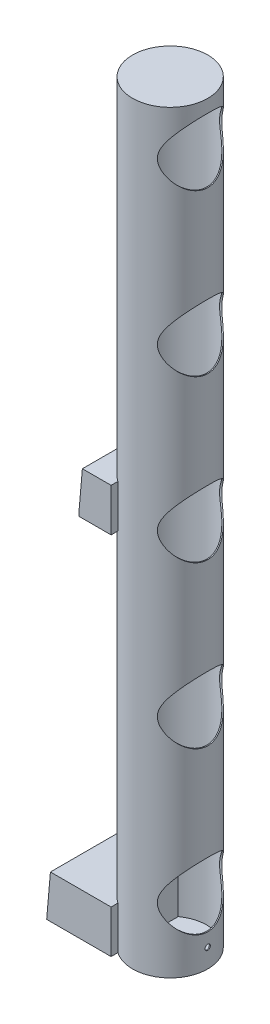
SolidWorks part; units mm, degrees
ref_plane "Спереди" through (0, 0, 0) normal (0, 0, 1) x (1, 0, 0)
ref_plane "Сверху" through (0, 0, 0) normal (0, 1, 0) x (1, 0, 0)
ref_plane "Справа" through (0, 0, 0) normal (1, 0, 0) x (0, 0, -1)
sketch "Эскиз2" plane through (0, 0, 0) normal (0, 1, 0) x (1, 0, 0)
  circle A0 centre (0, 0) radius 35
  circle A1 centre (0, 0) radius 34
  dimension "D1" = 70
  dimension "D2" = 68
extrude "Бобышка-Вытянуть1" add sketch "Эскиз2" along normal blind 700
sketch "Эскиз3" plane through (0, 0, 0) normal (0, -1, 0) x (1, 0, 0)
  circle A0 centre (0, 0) radius 35
extrude "Бобышка-Вытянуть2" add sketch "Эскиз3" along normal blind 1
sketch "Эскиз4" plane through (0, 700, 0) normal (0, 1, 0) x (1, 0, 0)
  circle A0 centre (0, 0) radius 35
extrude "Бобышка-Вытянуть3" add sketch "Эскиз4" along normal blind 1
sketch "Эскиз5" plane through (0, 0, 0) normal (1, 0, 0) x (0, 0, -1)
  line L0 (-35, -1) -> (35, -1) construction
  circle A0 centre (0, 16.5) radius 2.5
  circle A1 centre (0, 59) radius 30
  circle A2 centre (0, 209) radius 30
  circle A3 centre (0, 359) radius 30
  circle A4 centre (0, 509) radius 30
  circle A5 centre (0, 659) radius 30
  dimension "D1" = 5
  dimension "D2" = 15
  dimension "D3" = 60
  dimension "D4" = 60
  dimension "D6" = 150
  dimension "D5" = 5
extrude "Вырез-Вытянуть1" cut sketch "Эскиз5" along normal through all
sketch "Эскиз6" plane through (0, 0, 0) normal (1, 0, 0) x (0, 0, -1)
  line L0 (35, 701) -> (-35, 701) construction
  circle A0 centre (0, 686) radius 10
  dimension "D1" = 20
  dimension "D2" = 15
extrude "Вырез-Вытянуть2" cut sketch "Эскиз6" against normal through all
sketch "Эскиз7" plane through (0, 0, 0) normal (1, 0, 0) x (0, 0, -1)
  line L0 (-35, -1) -> (35, -1) construction
  line L1 (-35, 39) -> (35, 39)
  line L2 (-35, 39) -> (-35, -1)
  line L3 (-35, -1) -> (35, -1)
  line L4 (35, 39) -> (35, -1)
  line L5 (-35, 701) -> (-35, -1) construction
  line L10 (35, -1) -> (35, 701) construction
  dimension "D1" = 0
  dimension "D2" = 0
  dimension "D3" = 40
extrude "Бобышка-Вытянуть4" add sketch "Эскиз7" against normal blind 60 from offset 20 offset against normal yes
sketch "Эскиз8" plane through (0, 0, 0) normal (1, 0, 0) x (0, 0, -1)
  line L0 (35, -1) -> (35, 701) construction
  line L1 (-35, 379) -> (35, 379)
  line L2 (-35, 379) -> (-35, 339)
  line L3 (-35, 339) -> (35, 339)
  line L4 (35, 379) -> (35, 339)
  line L5 (-35, 701) -> (-35, -1) construction
  line L6 (-35, -1) -> (35, -1) construction
  dimension "D1" = 40
  dimension "D2" = 0
  dimension "D3" = 0
  dimension "D4" = 340
extrude "Бобышка-Вытянуть5" add sketch "Эскиз8" along normal blind 30 from offset 50 offset against normal yes
sketch "Эскиз9" plane through (0, 0, 0) normal (0, 0, 1) x (1, 0, 0)
  line L0 (-80, -1) -> (-76.5005, 39)
  line L3 (-50.2539, 339) -> (-46.7543, 379)
  line L6 (-80, 39) -> (-20, 39) construction
  line L7 (-80, -1) -> (-80, 39)
  line L8 (-80, 39) -> (-76.5005, 39)
  line L9 (-20, 379) -> (-50, 379) construction
  line L10 (-46.7543, 379) -> (-50, 379)
  line L11 (-50, 379) -> (-50.2539, 339)
  line L12 (-20, 339) -> (-50, 339) construction
  point P3 (-76.3489, 39)
  point P7 (-50, 339)
  dimension "D1" = 5
extrude "Вырез-Вытянуть3" cut sketch "Эскиз9" against normal through all both and the other way through all
